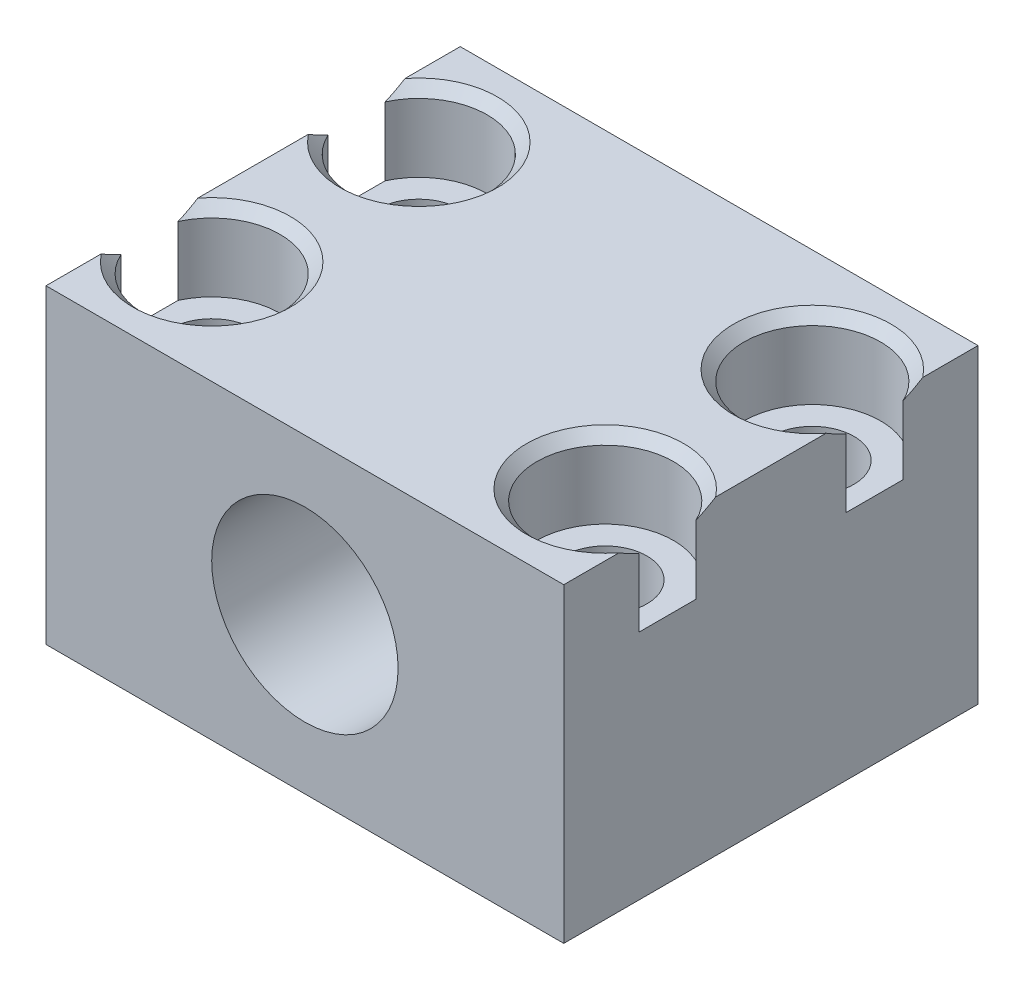
SolidWorks part; units mm, degrees
material "Gray Cast Iron"
ref_plane "Front Plane" through (0, 0, 0) normal (0, 0, 1) x (1, 0, 0)
ref_plane "Top Plane" through (0, 0, 0) normal (0, 1, 0) x (1, 0, 0)
ref_plane "Right Plane" through (0, 0, 0) normal (1, 0, 0) x (0, 0, -1)
sketch "Sketch1" plane through (0, 0, 0) normal (0, 0, 1) x (1, 0, 0)
  circle A0 centre (0, 0) radius 5.715
  circle A1 centre (0, 0) radius 18.669
  dimension "D3" = 11.43
  dimension "D1" = 37.338
extrude "nut-body-extrude" add sketch "Sketch1" along normal blind 25.4
sketch "Sketch2" plane through (0, 0, 0) normal (0, 0, 1) x (1, 0, 0)
  line L0 (0, 9.525) -> (0, 34.8179) construction
  line L1 (9.525, 0) -> (42.4926, 0) construction
  line L3 (-15.875, 9.525) -> (15.875, 9.525)
  line L4 (-15.875, 9.525) -> (-15.875, -9.525)
  line L5 (-15.875, -9.525) -> (15.875, -9.525)
  line L6 (15.875, 9.525) -> (15.875, -9.525)
  circle A1 centre (0, 0) radius 18.669
  circle A2 centre (0, 0) radius 18.669
  point P8 (-15.875, 0)
  point P9 (0, 9.525)
  dimension "D1" = 19.05
  dimension "D3" = 31.75
  dimension "D2" = 0
extrude "nut-trim-cut-extrude" cut sketch "Sketch2" along normal through all contours L3 A2 | L5 A2 | L6 A2 | L4 A2 region at (-18.141, 0, 0)
hole_wizard "CBORE for #10 Socket Head Cap Screw1" positions "Sketch5" profile "Sketch4" counterbore size "#10" standard "ANSI Inch" end condition through all
sketch "Sketch5" plane through (0, 9.525, 0) normal (0, 1, 0) x (1, 0, 0)
  line L0 (12.065, -6.35) -> (12.065, -19.05) construction
  line L1 (12.065, -19.05) -> (-12.065, -19.05) construction
  line L2 (-12.065, -19.05) -> (-12.065, -6.35) construction
  line L3 (-12.065, -6.35) -> (12.065, -6.35) construction
  line L4 (0, 0) -> (0, -12.7) construction
  line L5 (0, -12.7) -> (15.875, -12.7) construction
  line L6 (15.875, -25.4) -> (15.875, 0) construction
  line L7 (-5.715, 0) -> (-5.715, -25.4) construction
  line L8 (-5.715, 0) -> (-5.715, -25.4) construction
  line L9 (5.715, 0) -> (5.715, -25.4) construction
  point P0 (12.065, -6.35)
  point P2 (12.065, -19.05)
  point P4 (-12.065, -19.05)
  point P6 (-12.065, -6.35)
  point P29 (12.065, -12.7)
  point P43 (0, -6.35)
  dimension "D1" = 24.13
  dimension "D2" = 12.7
sketch "Sketch4" plane through (12.065, 9.525, 6.35) normal (1, 0, 0) x (0, 0, 1)
  line L0 (0, 0) -> (0, 19.05)
  line L1 (0, 19.05) -> (2.5527, 19.05)
  line L3 (2.5527, 19.05) -> (2.5527, 4.826)
  line L4 (4.191, 4.826) -> (2.5527, 4.826)
  line L5 (4.191, 4.826) -> (4.191, 0.635)
  line L6 (4.191, 0.635) -> (4.826, 0)
  line L7 (4.826, 0) -> (0, 0)
  line L8 (-4.191, 0.635) -> (-4.826, 0) construction
  line L11 (0, -6.35) -> (0, 107.95) construction
  dimension "Thru Hole Dia." = 5.1054
  dimension "Thru Hole Depth" = 19.05
  dimension "C'Bore Dia." = 8.382
  dimension "C'Bore Depth" = 4.826
  dimension "Near C'Sink Dia." = 9.652
  dimension "Near C'Sink Angle" = 90
equation "\"dovetail-angle\" = 60"
equation "\"dovetail-stock-width\" = 5"
equation "\"dovetail-stock-height\" = 1.25"
equation "\"dovetail-depth\" = 0.5 * \"dovetail-stock-height\""
equation "\"dovetail-throat-width\" = \"dovetail-stock-width\" - (2 * \"dovetail-depth\")"
equation "\"delta-x\" = 6"
equation "\"delta-y\" = 3"
equation "\"gib-thickness\" = 0.25"
equation "\"x-slide-length\" = \"dovetail-stock-width\" + \"delta-x\""
equation "\"y-slide-length\" = \"dovetail-stock-width\" + \"delta-y\""
equation "\"dog-point-diam\" = .149"
equation "\"dog-point-length\" = .067"
equation "\"dovetail-double-height\" = 2 * \"dovetail-depth\" + 0.5"
equation "\"acme-major-diam\" = .5"
equation "\"acme-pitch-diam\" = 0.45"
equation "\"acme-minor-diam\" = 0.4"
equation "\"acme-nut-od\" = 1.47"
equation "\"acme-nut-length\" = 1"
equation "\"D3@Sketch1\"=\"acme-pitch-diam\""
equation "\"D1@Sketch1\"=\"acme-nut-od\""
equation "\"D1@nut-body-extrude\"=\"acme-nut-length\""
equation "\"acme-nut-trim-height\" = .75"
equation "\"D1@Sketch2\"=\"acme-nut-trim-height\""
equation "\"screw-bearing-od\" = 0.5"
equation "\"screw-bearing-length\" = .375"
equation "\"screw-bearing-id\" = .375"
equation "\"end-plate-thickness\" = \"screw-bearing-length\""
equation "\"screw-add-length\" = 2 * \"end-plate-thickness\" + 1 + 0.5"
equation "\"x-screw-length\" = \"x-slide-length\" + \"screw-add-length\""
equation "\"y-screw-length\" = \"y-slide-length\" + \"screw-add-length\""
equation "\"acme-nut-mount-hole-space-vert\" = 0.5 * \"acme-nut-length\""
equation "\"D2@Sketch5\"=\"acme-nut-mount-hole-space-vert\""
equation "\"vise-hole-center-dist\" = 6.75"
equation "\"wiper_plate_clearance\" = .03"
equation "\"dial-width\" = 0.5"
equation "\"quarter-twenty-free-fit\" = .2667"
equation "\"acme-nut-mount-hole-space-horz\" = 0.95"
equation "\"D1@Sketch5\"=\"acme-nut-mount-hole-space-horz\""
